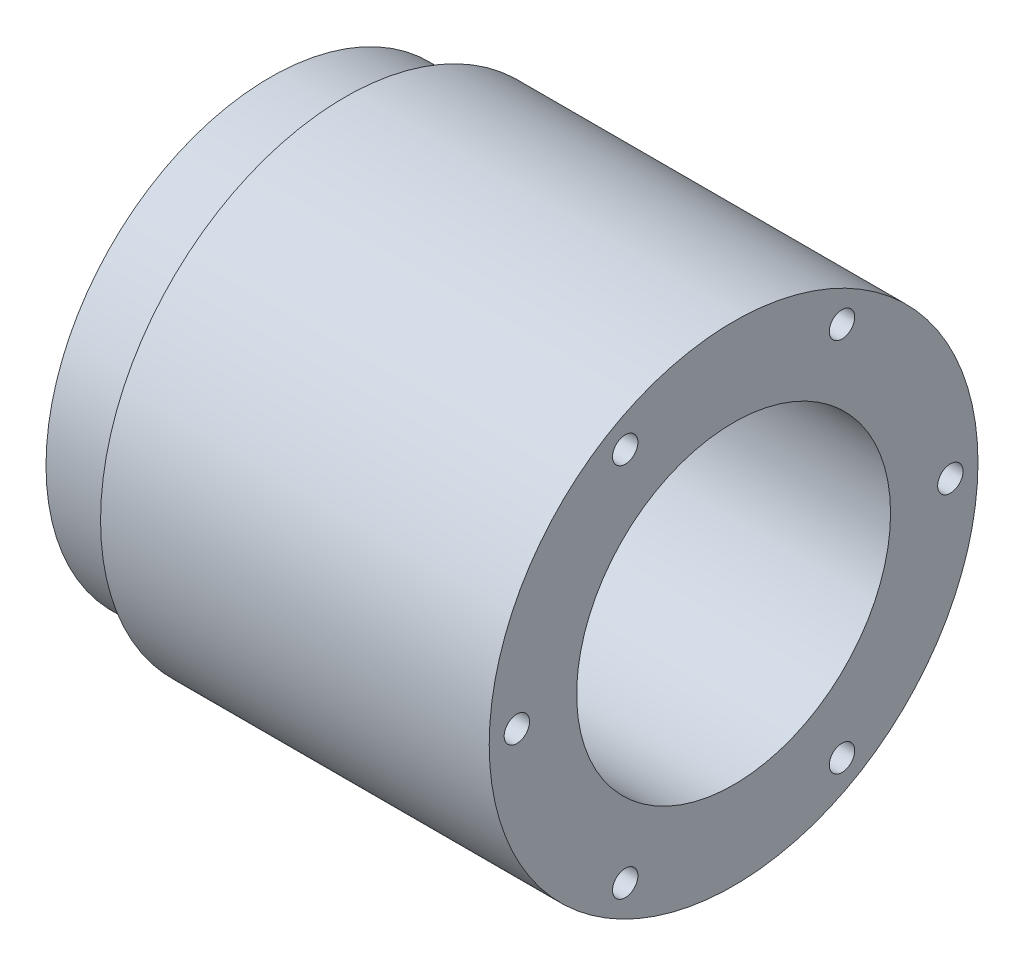
SolidWorks part; units mm, degrees
material "7075-O (SS)"
ref_plane "Front" through (0, 0, 0) normal (0, 0, 1) x (1, 0, 0)
ref_plane "Top" through (0, 0, 0) normal (0, 1, 0) x (1, 0, 0)
ref_plane "Right" through (0, 0, 0) normal (1, 0, 0) x (0, 0, -1)
sketch "Croquis1" plane through (0, 0, 0) normal (1, 0, 0) x (0, 0, -1)
  circle A0 centre (0, 0) radius 21
  circle A1 centre (0, 0) radius 32.7
  dimension "D1" = 42
  dimension "D2" = 65.4
extrude "Saliente-Extruir1" add sketch "Croquis1" along normal mid plane 47
sketch "Croquis3" plane through (-23.5, 0, 0) normal (-1, 0, 0) x (0, 0, 1)
  line L5 (0, -34.925) -> (0, 34.925) construction
  line L6 (-18, 21) -> (18, 21)
  line L15 (-21, 18) -> (-21, -18)
  line L16 (-18, -21) -> (18, -21)
  line L17 (21, 18) -> (21, -18)
  line L18 (34.925, 0) -> (-34.925, 0) construction
  arc A2 (18, -21) -> (21, -18) centre (18, -18) ccw
  arc A3 (-21, -18) -> (-18, -21) centre (-18, -18) ccw
  arc A4 (-18, 21) -> (-21, 18) centre (-18, 18) ccw
  arc A5 (18, 21) -> (21, 18) centre (18, 18) cw
  circle A6 centre (0, 0) radius 32.7 construction
  circle A7 centre (0, 0) radius 32.7
  point P4 (0, 21)
  point P7 (21, 0)
  point P12 (21, -21)
  point P19 (21, 21)
  dimension "D2" = 3
  dimension "D1" = 42
extrude "Saliente-Extruir3" add sketch "Croquis3" along normal blind 5
sketch "Croquis4" plane through (-23.5, 0, 0) normal (-1, 0, 0) x (0, 0, 1)
  line L1 (-15.5, -15.5) -> (15.5, -15.5) construction
  line L2 (-15.5, -15.5) -> (-15.5, 15.5) construction
  line L3 (-15.5, 15.5) -> (15.5, 15.5) construction
  line L4 (15.5, -15.5) -> (15.5, 15.5) construction
  line L5 (-15.5, -15.5) -> (15.5, 15.5) construction
  line L6 (-15.5, 15.5) -> (15.5, -15.5) construction
  circle A0 centre (15.5, 15.5) radius 3.5
  circle A1 centre (-15.5, 15.5) radius 3.5
  circle A2 centre (-15.5, -15.5) radius 3.5
  circle A3 centre (15.5, -15.5) radius 3.5
  point P0 (0, 0)
  dimension "D2" = 7
  dimension "D1" = 31
extrude "Cortar-Extruir1" cut sketch "Croquis4" against normal blind 6
ref_plane "Plano1" through (0, -21, 0) normal (0, 1, 0) x (1, 0, 0)
ref_plane "Plano2" through (0, -45, 0) normal (0, 1, 0) x (1, 0, 0)
sketch "Croquis20" plane through (0, 0, 0) normal (0, 1, 0) x (1, 0, 0)
  line L0 (10.0665, 0) -> (0, 0) construction
  line L1 (-37.9279, 0) -> (37.9279, 0) construction
  line L2 (0, 0) -> (0, -8.6641) construction
  line L3 (0, -35.97) -> (0, 35.97) construction
sketch "Croquis21" plane through (-28.5, 0, 0) normal (-1, 0, 0) x (0, 0, 1)
  line L8 (18, 21) -> (0, 21) construction
  line L9 (21, 0) -> (21, 18) construction
  line L10 (21, -18) -> (21, 0) construction
  line L11 (0, -21) -> (18, -21) construction
  line L12 (-18, -21) -> (0, -21) construction
  line L13 (-21, 0) -> (-21, -18) construction
  line L14 (-21, 18) -> (-21, 0) construction
  line L15 (0, 21) -> (-18, 21) construction
  line L16 (18, 21) -> (0, 21)
  line L17 (21, 0) -> (21, 18)
  line L18 (21, -18) -> (21, 0)
  line L19 (0, -21) -> (18, -21)
  line L20 (-18, -21) -> (0, -21)
  line L21 (-21, 0) -> (-21, -18)
  line L22 (-21, 18) -> (-21, 0)
  line L23 (0, 21) -> (-18, 21)
  circle A0 centre (0, 0) radius 30
  arc A9 (21, 18) -> (18, 21) centre (18, 18) ccw construction
  arc A10 (18, -21) -> (21, -18) centre (18, -18) ccw construction
  arc A11 (-21, -18) -> (-18, -21) centre (-18, -18) ccw construction
  arc A12 (-18, 21) -> (-21, 18) centre (-18, 18) ccw construction
  arc A13 (21, 18) -> (18, 21) centre (18, 18) ccw
  arc A14 (18, -21) -> (21, -18) centre (18, -18) ccw
  arc A15 (-21, -18) -> (-18, -21) centre (-18, -18) ccw
  arc A16 (-18, 21) -> (-21, 18) centre (-18, 18) ccw
  dimension "D1" = 60
extrude "Saliente-Extruir4" add sketch "Croquis21" along normal blind 10
hole_wizard "Taladro de margen para M31" positions "Croquis22" profile "Croquis24" hole size "M3" standard "Ansi Metric"
sketch "Croquis22" plane through (23.5, 0, 0) normal (1, 0, 0) x (0, 0, -1)
  line L2 (34.1, 0) -> (-34.1, 0) construction
  line L3 (0, 34.1) -> (0, -34.1) construction
  point P0 (29, 0)
  point P8 (14.5, -25.1147)
  point P9 (-14.5, -25.1147)
  point P10 (-29, 0)
  point P11 (-14.5, 25.1147)
  point P12 (14.5, 25.1147)
  point P18 (0, 0)
  point P19 (0, 0)
  point P20 (29.9461, 0)
  point P23 (-29.244, 0)
  dimension "D2" = 29
  dimension "D3" = 29
  dimension "D1" = 6
sketch "Croquis24" plane through (23.5, 0, -29) normal (0, 1, 0) x (0, 0, -1)
  line L0 (0, 0) -> (0, 11.0215)
  line L1 (0, 11.0215) -> (1.7, 10)
  line L2 (1.7, 10) -> (1.7, 0)
  line L5 (1.7, 0) -> (0, 0)
  line L10 (0, 11.0215) -> (-1.7, 10) construction
  line L11 (0, -6.35) -> (0, 107.95) construction
  dimension "Diámetro de taladro" = 3.4
  dimension "Profundidad de taladro" = 10
  dimension "Ángulo de perforador" = 118
